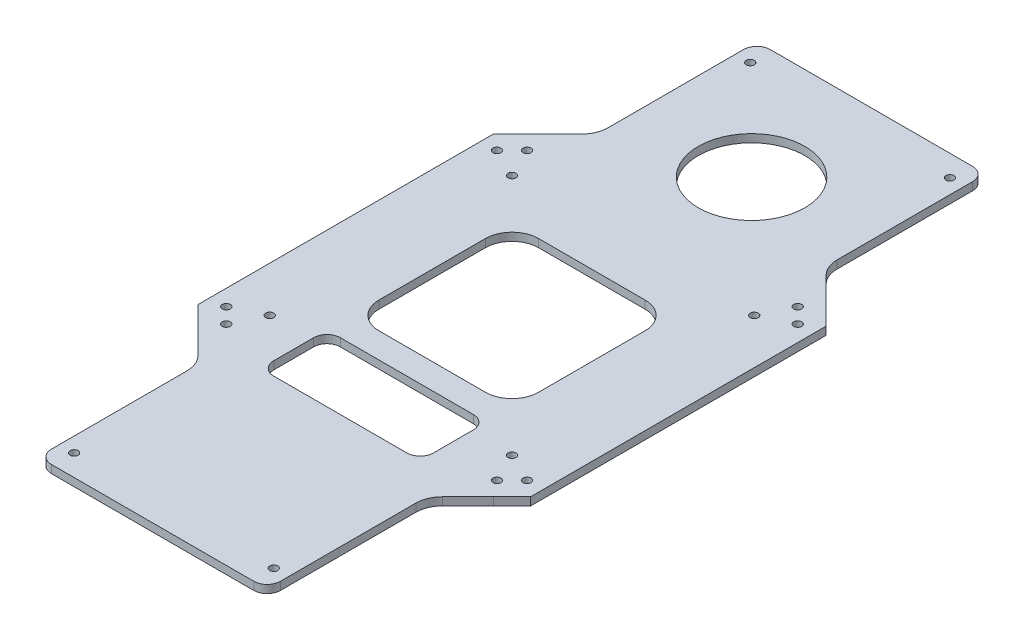
SolidWorks part; units mm, degrees
material "Thornel Mat VMA"
ref_plane "前视基准面" through (0, 0, 0) normal (0, 0, 1) x (1, 0, 0)
ref_plane "上视基准面" through (0, 0, 0) normal (0, 1, 0) x (1, 0, 0)
ref_plane "右视基准面" through (0, 0, 0) normal (1, 0, 0) x (0, 0, -1)
other "Configuration Table"
sketch "草图1" plane through (0, 0, 0) normal (0, 1, 0) x (1, 0, 0)
  line L0 (0, 0) -> (63.1315, 0) construction
  line L1 (-62.5, -62.5) -> (62.5, -62.5)
  line L2 (-62.5, -62.5) -> (-62.5, 62.5)
  line L3 (-62.5, 62.5) -> (62.5, 62.5)
  line L4 (62.5, -62.5) -> (62.5, 62.5)
  line L5 (-62.5, -62.5) -> (62.5, 62.5) construction
  line L6 (-62.5, 62.5) -> (62.5, -62.5) construction
  line L7 (0, 0) -> (0, 71.086) construction
  line L8 (50.8431, 56.5) -> (56.5, 50.8431) construction
  line L9 (43, 62.5) -> (43, 135)
  line L10 (43, 135) -> (-43, 135)
  line L11 (-43, 62.5) -> (-43, 135)
  line L12 (-43, -62.5) -> (-43, -135)
  line L13 (43, -135) -> (-43, -135)
  line L14 (43, -62.5) -> (43, -135)
  circle A4 centre (50.8431, 56.5) radius 1.5
  circle A5 centre (56.5, 50.8431) radius 1.5
  circle A6 centre (56.5, -50.8431) radius 1.5
  circle A7 centre (50.8431, -56.5) radius 1.5
  circle A8 centre (-50.8431, -56.5) radius 1.5
  circle A9 centre (-56.5, -50.8431) radius 1.5
  circle A10 centre (-56.5, 50.8431) radius 1.5
  circle A11 centre (-50.8431, 56.5) radius 1.5
  circle A12 centre (-37.5, 127) radius 1.5
  circle A13 centre (37.5, 127) radius 1.5
  circle A14 centre (37.5, -127) radius 1.5
  circle A15 centre (-37.5, -127) radius 1.5
  point P0 (0, 0)
  point P14 (0, 135)
  point P42 (0, -135)
  dimension "D3" = 72.5
  dimension "D5" = 3
  dimension "D6" = 3
  dimension "D7" = 3
  dimension "D8" = 8
  dimension "D13" = 75
  dimension "D1" = 125
  dimension "D2" = 125
  dimension "D4" = 86
  dimension "D9" = 45
  dimension "D10" = 6
  dimension "D11" = 6
  dimension "D12" = 127
extrude "凸台-拉伸1" add sketch "草图1" along normal blind 3 contours L1 L4 L3 L2 A10 A9 A8 A6 A5 A4 A7 A11 | L11 L3 L9 L10 | L14 L1 L12 L13 A14 A15 region at (0, 0, 0) region at (0, 0, 98.6858) region at (0, 0, -98.6858)
chamfer "倒角1" distance 7 angle 45 4 edges at (-62.5, 1.5, 62.5) (-62.5, 1.5, -62.5) (62.5, 1.5, 62.5) (62.5, 1.5, -62.5)
sketch "草图3" plane through (0, 3, 0) normal (0, 1, 0) x (1, 0, 0)
  line L0 (0, 0) -> (95.6793, 0) construction
  line L1 (0, 0) -> (0, 105.8926) construction
  line L18 (-49.5, -49.5) -> (49.5, -49.5)
  line L19 (-49.5, -49.5) -> (-49.5, 49.5)
  line L20 (-49.5, 49.5) -> (49.5, 49.5)
  line L21 (49.5, -49.5) -> (49.5, 49.5)
  line L22 (-49.5, -49.5) -> (49.5, 49.5) construction
  line L23 (-49.5, 49.5) -> (49.5, -49.5) construction
  line L24 (-30, -30) -> (30, -30)
  line L25 (-30, -30) -> (-30, 30)
  line L26 (-30, 30) -> (30, 30)
  line L27 (30, -30) -> (30, 30)
  line L28 (-30, -30) -> (30, 30) construction
  line L29 (-30, 30) -> (30, -30) construction
  line L36 (0, 0) -> (0, -149.5176) construction
  line L39 (-30, -39.5) -> (-30, -59.5)
  line L48 (-30, -39.5) -> (30, -39.5)
  line L49 (30, -39.5) -> (30, -59.5)
  line L50 (-30, -59.5) -> (30, -59.5)
  line L51 (-30, -59.5) -> (-30, -64.5)
  line L52 (-30, -64.5) -> (30, -64.5)
  line L53 (30, -64.5) -> (30, -59.5)
  circle A4 centre (-45.5, 45.5) radius 1.5
  circle A5 centre (45.5, 45.5) radius 1.5
  circle A6 centre (45.5, -45.5) radius 1.5
  circle A7 centre (-45.5, -45.5) radius 1.5
  circle A8 centre (0, 90) radius 20
  point P24 (-30, -49.5)
  point P26 (0, -59.5)
  point P30 (0, -39.5)
  dimension "D3" = 3
  dimension "D7" = 40
  dimension "D8" = 90
  dimension "D1" = 99
  dimension "D2" = 99
  dimension "D4" = 4
  dimension "D5" = 60
  dimension "D6" = 60
  dimension "D9" = 10
  dimension "D10" = 30
  dimension "D11" = 5
extrude "切除-拉伸1" cut sketch "草图3" against normal blind 3 contours L24 L27 L26 L25 | A4 | A5 | A6 | A7 | A8 | L49 L48 L39 L18 | L39 L50 L49 L18 | L52 L53 L50 L51 region at (0, 3, 44.5) region at (0, 3, 54.5) region at (0, 3, 62) region at (0, 3, 0) region at (-45.5, 3, -45.5) region at (45.5, 3, -45.5) region at (45.5, 3, 45.5) region at (-45.5, 3, 45.5) region at (0, 3, -90)
fillet "圆角3" radius 10 4 edges at (-30, 1.5, 30) (30, 1.5, 30) (30, 1.5, -30) (-30, 1.5, -30)
sketch "草图4" plane through (0, 3, 0) normal (0, 1, 0) x (1, 0, 0)
  line L0 (0, 0) -> (147.6965, 0) construction
  line L1 (0, 0) -> (0, 135.7677) construction
  line L2 (-50, 45) -> (70.2761, 45) construction
  line L7 (-50, 45) -> (-50, -77.0358) construction
  circle A0 centre (-41, 32.5) radius 1.5
  circle A1 centre (44, 30) radius 1.5
  circle A2 centre (-39, -27) radius 1.5
  circle A3 centre (39, -27) radius 1.5
  dimension "D1" = 3
  dimension "D3" = 12.5
  dimension "D5" = 3
  dimension "D8" = 3
  dimension "D10" = 3
  dimension "D12" = 72
  dimension "D2" = 9
  dimension "D4" = 94
  dimension "D6" = 15
  dimension "D7" = 11
  dimension "D9" = 72
  dimension "D11" = 89
  dimension "D13" = 50
  dimension "D14" = 45
fillet "圆角4" radius 5 4 edges at (-43, 1.5, 135) (43, 1.5, 135) (43, 1.5, -135) (-43, 1.5, -135)
fillet "圆角5" radius 5 4 edges at (-30, 1.5, 64.5) (30, 1.5, 64.5) (30, 1.5, 39.5) (-30, 1.5, 39.5)
chamfer "倒角2" distance 12.5 angle 45 4 edges at (43, 1.5, -62.5) (-43, 1.5, -62.5) (43, 1.5, 62.5) (-43, 1.5, 62.5)
fillet "圆角6" radius 10 4 edges at (-43, 1.5, -75) (43, 1.5, -75) (43, 1.5, 75) (-43, 1.5, 75)
